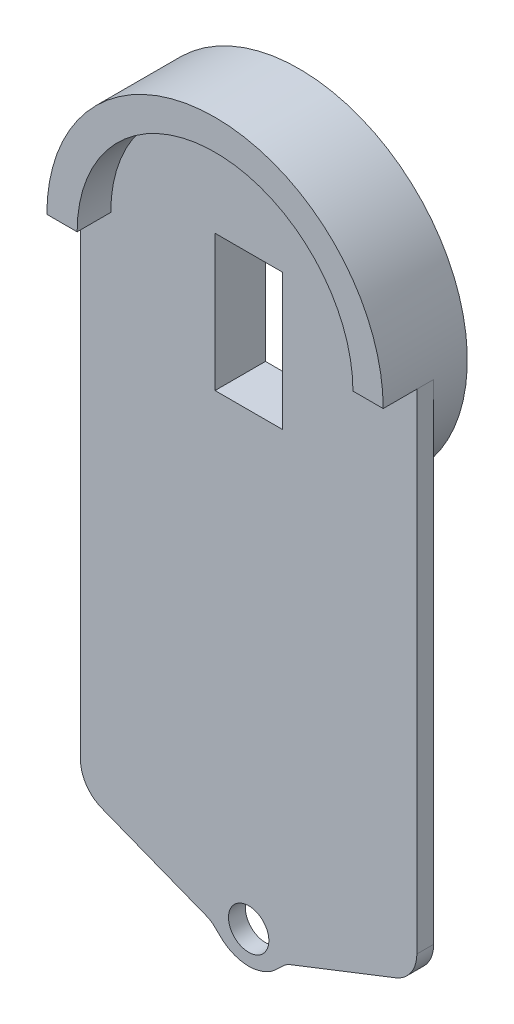
SolidWorks part; units mm, degrees
ref_plane "Alzado" through (0, 0, 0) normal (0, 0, 1) x (1, 0, 0)
ref_plane "Planta" through (0, 0, 0) normal (0, 1, 0) x (1, 0, 0)
ref_plane "Vista lateral" through (0, 0, 0) normal (1, 0, 0) x (0, 0, -1)
sketch "Croquis1" plane through (0, 0, 0) normal (0, 0, 1) x (1, 0, 0)
  line L12 (-50, 164) -> (-50, 11.7392)
  line L13 (13.7873, -2.4311) -> (20, 0)
  line L16 (-13.7873, -2.4311) -> (-20, 0)
  line L17 (-20, 0) -> (-50, 11.7392)
  line L18 (20, 0) -> (50, 11.7392)
  line L19 (50, 164) -> (50, 11.7392)
  circle A12 centre (0, 0) radius 6
  arc A15 (50, 164) -> (-50, 164) centre (0, 164) ccw
  arc A16 (-8.8548, -5.6773) -> (8.8548, -5.6773) centre (0, 2.4216) ccw
  spline S3 degree 3 poles (8.8548, -5.6773) (9.5176, -5.0903) (10.9007, -3.469) (12.7112, -2.8522) (13.7873, -2.4311) knots 0.517709 0.517709 0.517709 0.517709 0.741172 1 1 1 1
  spline S4 degree 3 poles (-8.8548, -5.6773) (-9.5176, -5.0903) (-10.9007, -3.469) (-12.7112, -2.8522) (-13.7873, -2.4311) knots 0.517709 0.517709 0.517709 0.517709 0.741172 1 1 1 1
  dimension "D1" = 12
  dimension "D6" = 100
  dimension "D3" = 20
  dimension "D4" = 164
extrude "Saliente-Extruir1" add sketch "Croquis1" along normal blind 5 contours L13 L18 L19 A15 L12 L17 L16 A12 region at (0, 103.1835, 0)
fillet "Redondeo1" radius 10 1 edges at (50, 11.7392, 2.5) type face fillet first side face at (50, 87.8696, 2.5) second side face at (31.8937, 4.6541, 2.5)
fillet "Redondeo3" radius 10 1 edges at (-50, 11.7392, 2.5)
sketch "Croquis2" plane through (0, 0, 5) normal (0, 0, 1) x (1, 0, 0)
  circle A0 centre (0, 164) radius 50
  circle A1 centre (0, 164) radius 41
  dimension "D1" = 100
  dimension "D2" = 82
extrude "Saliente-Extruir3" add sketch "Croquis2" along normal blind 10
sketch "Croquis3" plane through (0, 0, 0) normal (0, 0, -1) x (-1, 0, 0)
  line L0 (-10, 174.1411) -> (10, 174.1411)
  line L1 (10, 174.1411) -> (10, 133.6411)
  line L2 (10, 133.6411) -> (-10, 133.6411)
  line L3 (-10, 133.6411) -> (-10, 174.1411)
extrude "Cortar-Extruir1" cut sketch "Croquis3" against normal blind 10
sketch "Croquis4" plane through (0, 0, 15) normal (0, 0, 1) x (1, 0, 0)
  line L0 (-41, 164) -> (-50, 164)
  line L1 (41, 164) -> (50, 164)
  arc A0 (-50, 164) -> (50, 164) centre (0, 164) ccw
  arc A1 (-41, 164) -> (41, 164) centre (0, 164) ccw
extrude "Cortar-Extruir2" cut sketch "Croquis4" against normal blind 10
sketch "Croquis5" plane through (0, 0, 0) normal (0, 0, -1) x (-1, 0, 0)
  line L0 (-10, 174.1411) -> (-8, 174.1411)
  line L1 (10, 174.1411) -> (10, 133.6411)
  line L2 (10, 133.6411) -> (-10, 133.6411)
  line L3 (-10, 133.6411) -> (-10, 174.1411)
  line L4 (8, 174.1411) -> (10, 174.1411)
  line L5 (-8, 194.1411) -> (8, 194.1411)
  line L6 (-8, 194.1411) -> (-8, 174.1411)
  line L7 (8, 194.1411) -> (8, 174.1411)
  circle A0 centre (0, 164) radius 50
  dimension "D1" = 16
extrude "Saliente-Extruir4" add sketch "Croquis5" along normal blind 10
